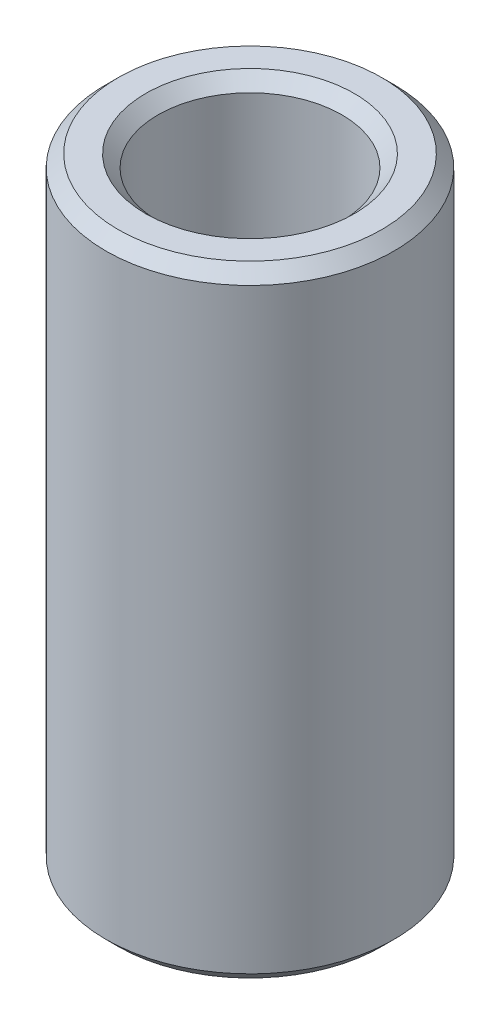
SolidWorks part; units mm, degrees
ref_plane "Front Plane" through (0, 0, 0) normal (0, 0, 1) x (1, 0, 0)
ref_plane "Top Plane" through (0, 0, 0) normal (0, 1, 0) x (1, 0, 0)
ref_plane "Right Plane" through (0, 0, 0) normal (1, 0, 0) x (0, 0, -1)
sketch "Sketch1" plane through (0, 0, 0) normal (0, 1, 0) x (1, 0, 0)
  circle A0 centre (0, 0) radius 30
  dimension "SLEEVE_OD" = 60
extrude "Boss-Extrude1" add sketch "Sketch1" along normal blind 129.2452
sketch "Sketch2" plane through (0, 0, 0) normal (0, 1, 0) x (1, 0, 0)
  circle A0 centre (0, 0) radius 19.1358
  dimension "BORE_D" = 38.2717
extrude "Cut-Extrude1" cut sketch "Sketch2" along normal through all
chamfer "Chamfer1" distance 2.5694 angle 45 4 edges at (0, 129.2452, 19.1358) (0, 0, 19.1358) (0, 0, 30) (0, 129.2452, 30)
